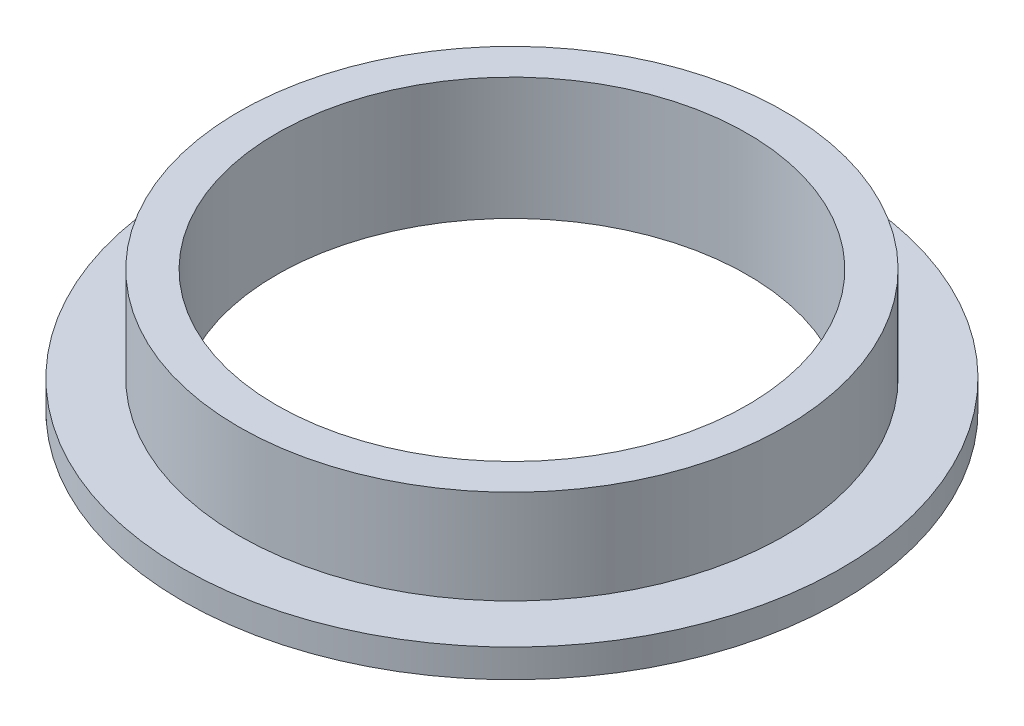
SolidWorks part; units mm, degrees
ref_plane "Front Plane" through (0, 0, 0) normal (0, 0, 1) x (1, 0, 0)
ref_plane "Top Plane" through (0, 0, 0) normal (0, 1, 0) x (1, 0, 0)
ref_plane "Right Plane" through (0, 0, 0) normal (1, 0, 0) x (0, 0, -1)
sketch "Sketch1" plane through (0, 0, 0) normal (0, 1, 0) x (1, 0, 0)
  circle A0 centre (0, 0) radius 35
  circle A1 centre (0, 0) radius 30 construction
  circle A2 centre (0, 0) radius 25
  dimension "D1" = 70
  dimension "D2" = 60
  dimension "D3" = 50
extrude "Boss-Extrude1" add sketch "Sketch1" along normal blind 3
sketch "Sketch2" plane through (0, 3, 0) normal (0, 1, 0) x (1, 0, 0)
  circle A0 centre (0, 0) radius 29
  circle A1 centre (0, 0) radius 25
  dimension "D1" = 58
  dimension "D2" = 50
extrude "Boss-Extrude2" add sketch "Sketch2" along normal blind 10
